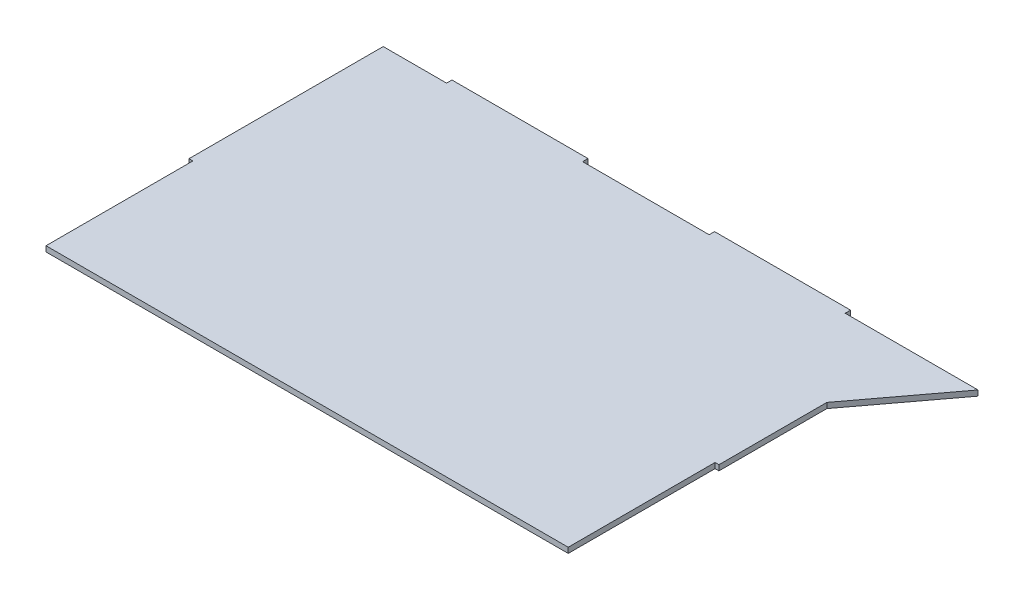
SolidWorks part; units mm, degrees
material "6061-T6 (SS)"
ref_plane "X-Y Datum" through (0, 0, 0) normal (0, 0, 1) x (1, 0, 0)
ref_plane "X-Z Datum" through (0, 0, 0) normal (0, 1, 0) x (1, 0, 0)
ref_plane "Y-Z Datum" through (0, 0, 0) normal (1, 0, 0) x (0, 0, -1)
sketch "Sketch1" plane through (0, 0, 0) normal (0, 0, 1) x (1, 0, 0)
  line L1 (-155.8379, -1.5875) -> (155.8379, -1.5875)
  line L2 (-155.8379, -1.5875) -> (-155.8379, 1.5875)
  line L3 (-155.8379, 1.5875) -> (155.8379, 1.5875)
  line L4 (155.8379, -1.5875) -> (155.8379, 1.5875)
  line L5 (-155.8379, -1.5875) -> (155.8379, 1.5875) construction
  line L6 (-155.8379, 1.5875) -> (155.8379, -1.5875) construction
  point P0 (0, 0)
  dimension "D1" = 311.6759
  dimension "D2" = 3.175
extrude "Boss-Extrude1" add sketch "Sketch1" along normal blind 200.6
sketch "Sketch3" plane through (0, 0, 0) normal (0, 0, -1) x (-1, 0, 0)
  line L0 (-155.8379, 0) -> (-75.8379, 0) construction
  line L1 (-155.8379, -1.5875) -> (-155.8379, 1.5875) construction
  line L2 (-155.8379, 1.5875) -> (155.8379, 1.5875) construction
  line L3 (-115.8379, -1.5875) -> (-35.8379, -1.5875)
  line L4 (-115.8379, -1.5875) -> (-115.8379, 1.5875)
  line L5 (-115.8379, 1.5875) -> (-35.8379, 1.5875)
  line L6 (-35.8379, -1.5875) -> (-35.8379, 1.5875)
  line L7 (-115.8379, -1.5875) -> (-35.8379, 1.5875) construction
  line L8 (-115.8379, 1.5875) -> (-35.8379, -1.5875) construction
  line L14 (-155.8379, 1.5875) -> (-115.8379, 1.5875)
  line L15 (-155.8379, 1.5875) -> (-155.8379, -1.5875)
  line L16 (-155.8379, -1.5875) -> (-115.8379, -1.5875)
  line L17 (-115.8379, 1.5875) -> (-115.8379, -1.5875)
  line L19 (-35.8379, 1.5875) -> (-35.8379, -1.5875)
  line M3 (-155.8379, -1.5875) -> (155.8379, -1.5875)
  line M5 (155.8379, 1.5875) -> (-155.8379, 1.5875)
  dimension "D1" = 40
  dimension "D2" = 80
sketch "Sketch5" plane through (0, 1.5875, 0) normal (0, 1, 0) x (1, 0, 0)
  line L1 (-155.8379, -200.6) -> (-153.5519, -200.6)
  line L3 (-155.8379, -200.6) -> (-155.8379, -114.24)
  line L5 (-155.8379, -114.24) -> (-153.5519, -114.24)
  line L6 (-153.5519, -200.6) -> (-153.5519, -114.24)
  line M11 (-155.8379, 0) -> (-155.8379, -200.6)
  line M12 (-155.8379, -200.6) -> (155.8379, -200.6)
  dimension "D1" = 86.36
  dimension "D2" = 2.286
extrude "Cut-Extrude2" cut sketch "Sketch5" against normal blind 3.175 and the other way through all contours M12 M11 region at (-154.6949, 1.5875, 157.42)
mirror "Mirror1" about plane through (0, 0, 0) normal (1, 0, 0) of "Cut-Extrude2"
sketch "Sketch6" plane through (0, 1.5875, 0) normal (0, 1, 0) x (1, 0, 0)
  line L6 (-155.8379, -180.28) -> (-79.6379, -180.28)
  line L7 (-155.8379, -180.28) -> (-155.8379, -200.6)
  line L8 (-155.8379, -200.6) -> (-79.6379, -200.6)
  line L9 (-79.6379, -180.28) -> (-79.6379, -200.6)
  line L10 (153.5519, -200.6) -> (-153.5519, -200.6) construction
  line L11 (-155.8379, -114.24) -> (-155.8379, 0) construction
  line L13 (153.5519, -200.6) -> (-79.6379, -200.6)
  line L14 (153.5519, -200.6) -> (153.5519, -180.28)
  line L15 (153.5519, -180.28) -> (-79.6379, -180.28)
  line L16 (-79.6379, -200.6) -> (-79.6379, -180.28)
  line M18 (-153.5519, -114.24) -> (-153.5519, -200.6)
  line M19 (-153.5519, -200.6) -> (153.5519, -200.6)
  dimension "D1" = 76.2
  dimension "D2" = 20.32
extrude "Cut-Extrude4" [suppressed] cut sketch "Sketch6" against normal through all contours L9 L6 M18 M19
sketch "Sketch7" [suppressed] plane through (0, 1.5875, 0) normal (0, 1, 0) x (1, 0, 0)
  line L1 (-81.2823, -215.455) -> (155.1963, -215.455)
  line L2 (-81.2823, -215.455) -> (-81.2823, -235.775)
  line L3 (-81.2823, -235.775) -> (155.1963, -235.775)
  line L4 (155.1963, -215.455) -> (155.1963, -235.775)
extrude "Cut-Extrude5" [suppressed] cut sketch "Sketch7" against normal through all
sketch "Sketch8" [suppressed] plane through (0, 1.5875, 0) normal (0, 1, 0) x (1, 0, 0)
  line L0 (155.1963, -235.775) -> (-155.1963, -235.775) construction
  line L1 (157.4823, -215.455) -> (81.2823, -215.455)
  line L2 (157.4823, -215.455) -> (157.4823, -235.775)
  line L3 (157.4823, -235.775) -> (81.2823, -235.775)
  line L4 (81.2823, -215.455) -> (81.2823, -235.775)
  line L5 (157.4823, -117.411) -> (157.4823, -3.175) construction
  dimension "D1" = 20.32
  dimension "D2" = 76.2
extrude "Cut-Extrude6" [suppressed] cut sketch "Sketch8" against normal through all
sketch "Sketch9" [suppressed] plane through (0, 0, 215.455) normal (0, 0, 1) x (1, 0, 0)
  line L4 (155.1963, 1.5875) -> (-155.1963, 1.5875)
  line L5 (-155.1963, 1.5875) -> (-155.1963, -1.5875)
  line L6 (-155.1963, -1.5875) -> (155.1963, -1.5875)
  line L7 (155.1963, -1.5875) -> (155.1963, 1.5875)
  line L8 (155.1963, 1.5875) -> (-155.1963, 1.5875)
  line L9 (-155.1963, 1.5875) -> (-155.1963, -1.5875)
  line L10 (-155.1963, -1.5875) -> (155.1963, -1.5875)
  line L11 (155.1963, -1.5875) -> (155.1963, 1.5875)
  dimension "D1" = 0
extrude "Cut-Extrude7" [suppressed] cut sketch "Sketch9" against normal blind 11.68
extrude "Boss-Extrude2" add sketch "Sketch3" along normal blind 3.175 contours L6 L4 M3 M5 region at (75.8379, 0, 0)
pattern_linear "LPattern2" count 2 spacing 154.43 along (-1, 0, 0) of "Boss-Extrude2"
sketch "Sketch10" plane through (0, -1.5875, 0) normal (0, -1, 0) x (1, 0, 0)
  line L8 (155.8379, 0) -> (193.9379, 0)
  line L9 (193.9379, 0) -> (155.8379, 50.8)
  line L10 (155.8379, 114.24) -> (155.8379, 0) construction
  line L11 (155.8379, 50.8) -> (155.8379, 0)
  dimension "D1" = 50.8
  dimension "D2" = 38.1
extrude "Boss-Extrude3" add sketch "Sketch10" against normal blind 3.175
sketch "Sketch11" [suppressed] plane through (0, 0, 0) normal (0, 0, -1) x (-1, 0, 0)
  line L1 (37.2652, -1.5875) -> (117.2652, -1.5875)
  line L2 (37.2652, -1.5875) -> (37.2652, 1.5875)
  line L3 (37.2652, 1.5875) -> (117.2652, 1.5875)
  line L4 (117.2652, -1.5875) -> (117.2652, 1.5875)
  line L5 (-117.1668, -1.5875) -> (-37.1668, -1.5875)
  line L6 (-117.1668, -1.5875) -> (-117.1668, 1.5875)
  line L7 (-117.1668, 1.5875) -> (-37.1668, 1.5875)
  line L8 (-37.1668, -1.5875) -> (-37.1668, 1.5875)
extrude "Boss-Extrude4" [suppressed] add sketch "Sketch11" along normal blind 3.175
